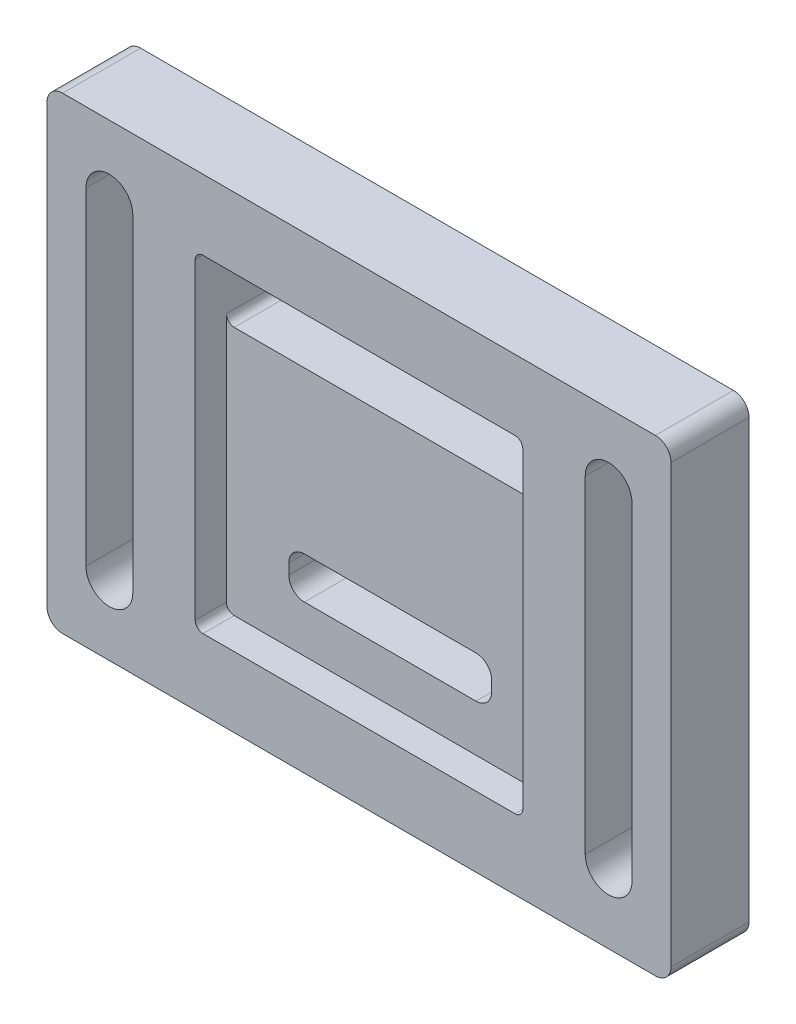
SolidWorks part; units mm, degrees
ref_plane "Piano frontale" through (0, 0, 0) normal (0, 0, 1) x (1, 0, 0)
ref_plane "Piano superiore" through (0, 0, 0) normal (0, 1, 0) x (1, 0, 0)
ref_plane "Piano destro" through (0, 0, 0) normal (1, 0, 0) x (0, 0, -1)
sketch "Schizzo2" plane through (0, 0, 0) normal (0, 0, 1) x (1, 0, 0)
  line L0 (4, 25.5) -> (4, 4.5) construction
  line L3 (0, 0) -> (40, 0)
  line L4 (0, 0) -> (0, 30)
  line L5 (0, 30) -> (40, 30)
  line L6 (40, 0) -> (40, 30)
  line L7 (9.5, 25.5) -> (30.5, 25.5)
  line L8 (9.5, 25.5) -> (9.5, 4.5)
  line L9 (9.5, 4.5) -> (30.5, 4.5)
  line L10 (30.5, 25.5) -> (30.5, 4.5)
  line L11 (9.5, 25.5) -> (30.5, 25.5)
  line L12 (9.5, 25.5) -> (9.5, 20.5)
  line L13 (9.5, 20.5) -> (30.5, 20.5)
  line L14 (30.5, 25.5) -> (30.5, 20.5)
  line L15 (13.5, 10.1735) -> (26.5, 10.1735)
  line L16 (13.5, 10.1735) -> (13.5, 7.5)
  line L17 (13.5, 7.5) -> (26.5, 7.5)
  line L18 (26.5, 10.1735) -> (26.5, 7.5)
  line L19 (5.5, 25.5) -> (5.5, 4.5)
  line L20 (2.5, 25.5) -> (2.5, 4.5)
  line L21 (36, 25.5) -> (36, 4.5) construction
  line L22 (37.5, 25.5) -> (37.5, 4.5)
  line L23 (34.5, 25.5) -> (34.5, 4.5)
  arc A2 (5.5, 25.5) -> (2.5, 25.5) centre (4, 25.5) ccw
  arc A3 (2.5, 4.5) -> (5.5, 4.5) centre (4, 4.5) ccw
  arc A4 (37.5, 25.5) -> (34.5, 25.5) centre (36, 25.5) ccw
  arc A5 (34.5, 4.5) -> (37.5, 4.5) centre (36, 4.5) ccw
  point P18 (4, 15)
  point P23 (36, 15)
  dimension "D1" = 40
  dimension "D2" = 30
  dimension "D3" = 21
  dimension "D4" = 21
  dimension "D5" = 4.5
  dimension "D6" = 9.5
  dimension "D7" = 5
  dimension "D8" = 3
  dimension "D9" = 4
  dimension "D10" = 4
  dimension "D11" = 4
  dimension "D12" = 4
  dimension "D13" = 1.5
  dimension "D14" = 1.5
extrude "Estrusione-Estrusione1" add sketch "Schizzo2" along normal blind 5 contours L3 L6 L5 L4 A5 L23 A4 L22 A3 L20 A2 L19 L7 L10 L9 L8 region at (0.5, 15, 0)
extrude "Estrusione-Estrusione2" add sketch "Schizzo2<3>" along normal blind 3 contours L13 L8 L9 L10 L15 L18 L17 L16 region at (20, 12.9226, 0)
sketch "Schizzo2<3>" plane through (0, 0, 0) normal (0, 0, 1) x (1, 0, 0) same geometry as "Schizzo2"
fillet "Raccordo2" radius 1 4 edges at (13.5, 10.1735, 1.5) (26.5, 10.1735, 1.5) (26.5, 7.5, 1.5) (13.5, 7.5, 1.5)
fillet "Raccordo3" radius 1 4 edges at (0, 30, 2.5) (40, 30, 2.5) (40, 0, 2.5) (0, 0, 2.5)
fillet "Raccordo4" radius 0.5 6 edges at (30.5, 20.5, 1.5) (9.5, 20.5, 1.5) (30.5, 25.5, 2.5) (9.5, 25.5, 2.5) (30.5, 4.5, 4) (9.5, 4.5, 4)
